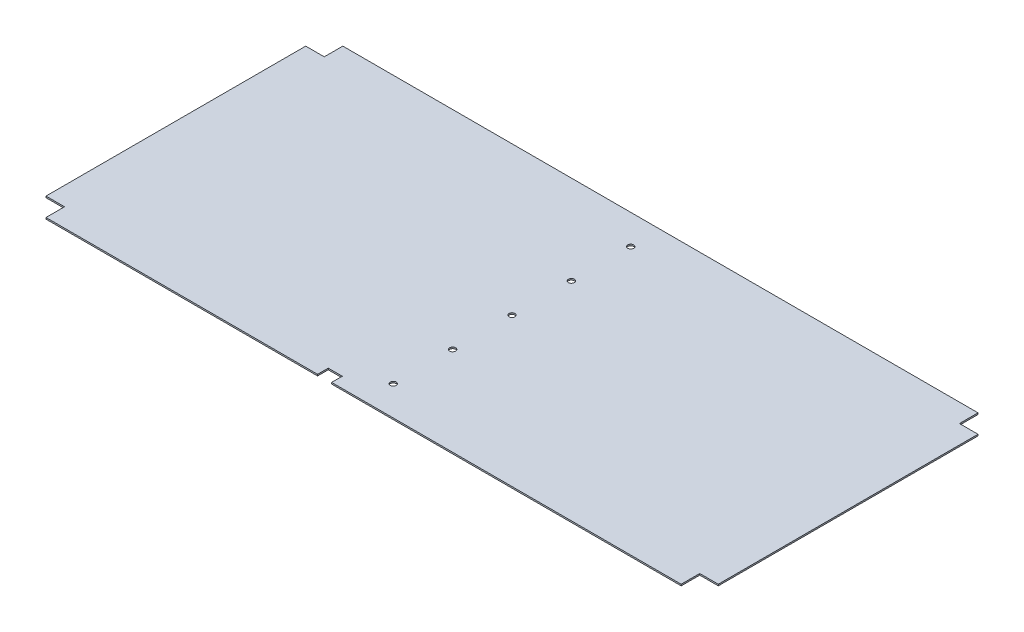
SolidWorks part; units mm, degrees
ref_plane "Ön Düzlem" through (0, 0, 0) normal (0, 0, 1) x (1, 0, 0)
ref_plane "Üst Düzlem" through (0, 0, 0) normal (0, 1, 0) x (1, 0, 0)
ref_plane "Sağ Düzlem" through (0, 0, 0) normal (1, 0, 0) x (0, 0, -1)
sketch "Çizim1" plane through (0, 0, 0) normal (0, 1, 0) x (1, 0, 0)
  line L1 (-453, 400) -> (453, 400)
  line L2 (-453, 400) -> (-453, 0)
  line L3 (-453, 0) -> (453, 0)
  line L4 (453, 400) -> (453, 0)
  point P4 (0, 0)
  dimension "D1" = 906
  dimension "D2" = 400
base flange "Taban-Flanş1" sketch "Çizim1" thickness 2 reverse thickness direction no parameters "D1"=0.7366
sketch "Çizim6" plane through (0, -2, 0) normal (0, -1, 0) x (1, 0, 0)
  line L0 (-453, -200) -> (-223.3794, -200) construction
  line L1 (-453, 0) -> (-428, 0)
  line L2 (-453, 0) -> (-453, -25)
  line L3 (-453, -25) -> (-428, -25)
  line L4 (-428, 0) -> (-428, -25)
  line L5 (-453, -400) -> (-453, 0) construction
  line L6 (0, 0) -> (0, -327.5766) construction
  line L7 (453, -25) -> (428, -25)
  line L8 (428, 0) -> (428, -25)
  line L9 (453, 0) -> (428, 0)
  line L10 (453, 0) -> (453, -25)
  line L11 (453, -400) -> (453, -375)
  line L12 (453, -400) -> (428, -400)
  line L13 (428, -400) -> (428, -375)
  line L14 (453, -375) -> (428, -375)
  line L15 (-453, -375) -> (-428, -375)
  line L16 (-428, -400) -> (-428, -375)
  line L17 (-453, -400) -> (-428, -400)
  line L18 (-453, -400) -> (-453, -375)
  dimension "D1" = 25
  dimension "D2" = 25
extrude "Kes-Ekstrüzyon1" cut sketch "Çizim6" against normal blind 10 normal cut yes
sketch "Çizim7" plane through (0, 0, 0) normal (0, 1, 0) x (1, 0, 0)
  line L0 (428, 400) -> (-428, 400) construction
  line L1 (-428, 0) -> (428, 0) construction
  line L2 (453, 25) -> (453, 375) construction
  circle A0 centre (0, 360) radius 4
  circle A1 centre (0, 280) radius 4
  circle A2 centre (0, 200) radius 4
  circle A3 centre (0, 120) radius 4
  circle A4 centre (0, 40) radius 4
  dimension "D1" = 8
  dimension "D3" = 40
  dimension "D4" = 40
  dimension "D5" = 453
  dimension "D2" = 5
extrude "Kes-Ekstrüzyon2" cut sketch "Çizim7" against normal blind 10 normal cut yes
sketch "Çizim8" plane through (0, 0, 0) normal (0, 1, 0) x (1, 0, 0)
  line L1 (-43.0485, 14.372) -> (-62, 14.372)
  line L2 (-43.0485, 14.372) -> (-43.0485, -7.5)
  line L3 (-43.0485, -7.5) -> (-62, -7.5)
  line L4 (-62, 14.372) -> (-62, -7.5)
extrude "Kes-Ekstrüzyon3" cut sketch "Çizim8" against normal blind 10 normal cut yes
sketch "Büküm-Çizgileri1" [suppressed] plane through (0, 0, 0) normal (0, 1, 0) x (1, 0, 0)
sketch "Sınırlandırma-Kutusu1" [suppressed] plane through (0, 0, 0) normal (0, 1, 0) x (1, 0, 0)
sheet metal parameters "Sac-Levha1" thickness 2 parameters "D1"=0.7366
flat pattern "Düz-Çoğaltma1" [suppressed]
sketch "Büküm-Çizgileri2" plane through (0, 0, 0) normal (0, 1, 0) x (1, 0, 0)
sketch3d "Sınırlandırma-Kutusu2" [suppressed]
  line L0 (-453, 0, 0) -> (453, 0, 0) construction
  line L1 (-453, 400, 0) -> (453, 400, 0) construction
  line L2 (-453, 0, 0) -> (-453, 400, 0) construction
  line L3 (453, 0, 0) -> (453, 400, 0) construction
sheet metal parameters "Sac-Levha2" thickness 2 parameters "D1"=0.7366
flat pattern "Düz-Çoğaltma1"
sketch "Büküm-Çizgileri2" plane through (0, 0, 0) normal (0, 1, 0) x (1, 0, 0)
sketch3d "Sınırlandırma-Kutusu2" [suppressed]
  line L0 (453, 0, 0) -> (-453, 0, 0) construction
  line L1 (453, 400, 0) -> (-453, 400, 0) construction
  line L2 (453, 0, 0) -> (453, 400, 0) construction
  line L3 (-453, 0, 0) -> (-453, 400, 0) construction
sheet metal parameters "Sac-Levha3" thickness 2 parameters "D1"=0.7366
flat pattern "Düz-Çoğaltma1"
sketch "Büküm-Çizgileri2" plane through (0, 0, 0) normal (0, 1, 0) x (1, 0, 0)
sketch3d "Sınırlandırma-Kutusu2" [suppressed]
  line L0 (453, 0, 0) -> (-453, 0, 0) construction
  line L1 (453, 400, 0) -> (-453, 400, 0) construction
  line L2 (453, 0, 0) -> (453, 400, 0) construction
  line L3 (-453, 0, 0) -> (-453, 400, 0) construction
sheet metal parameters "Sac-Levha4" thickness 2 parameters "D1"=0.7366
flat pattern "Düz-Çoğaltma1"
sketch "Büküm-Çizgileri2" plane through (0, 0, 0) normal (0, 1, 0) x (1, 0, 0)
sketch3d "Sınırlandırma-Kutusu2" [suppressed]
  line L0 (453, 0, 0) -> (-453, 0, 0) construction
  line L1 (453, 400, 0) -> (-453, 400, 0) construction
  line L2 (453, 0, 0) -> (453, 400, 0) construction
  line L3 (-453, 0, 0) -> (-453, 400, 0) construction
